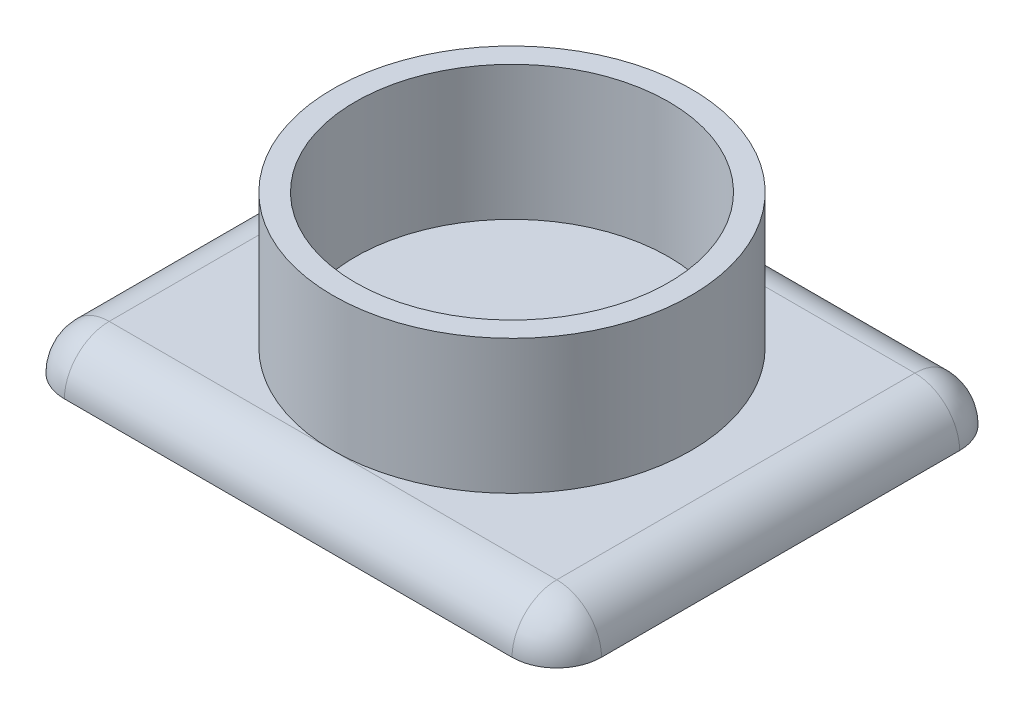
SolidWorks part; units mm, degrees
ref_plane "Front Plane" through (0, 0, 0) normal (0, 0, 1) x (1, 0, 0)
ref_plane "Top Plane" through (0, 0, 0) normal (0, 1, 0) x (1, 0, 0)
ref_plane "Right Plane" through (0, 0, 0) normal (1, 0, 0) x (0, 0, -1)
sketch "Sketch1" plane through (0, 0, 0) normal (0, 1, 0) x (1, 0, 0)
  circle A0 centre (0, 0) radius 40
  circle A1 centre (0, 0) radius 35
  dimension "D1" = 80
extrude "Boss-Extrude1" add sketch "Sketch1" along normal blind 30
sketch "Sketch2" plane through (0, 0, 0) normal (0, -1, 0) x (1, 0, 0)
  line L1 (60, -50) -> (-60, -50)
  line L2 (60, -50) -> (60, 50)
  line L3 (60, 50) -> (-60, 50)
  line L4 (-60, -50) -> (-60, 50)
  line L5 (60, -50) -> (-60, 50) construction
  line L6 (60, 50) -> (-60, -50) construction
  point P0 (0, 0)
  dimension "D1" = 120
  dimension "D2" = 100
  dimension "D3" = 100
  dimension "D4" = 120
extrude "Boss-Extrude2" add sketch "Sketch2" along normal blind 10 contours L3 L4 L1 L2
fillet "Fillet4" radius 10 4 edges at (-60, -5, 50) (-60, -5, -50) (60, -5, -50) (60, -5, 50)
fillet "Fillet5" radius 10 8 edges at (57.0711, 0, -47.0711) (0, 0, -50) (-57.0711, 0, -47.0711) (-60, 0, 0) (-57.0711, 0, 47.0711) (0, 0, 50) (57.0711, 0, 47.0711) (60, 0, 0)
